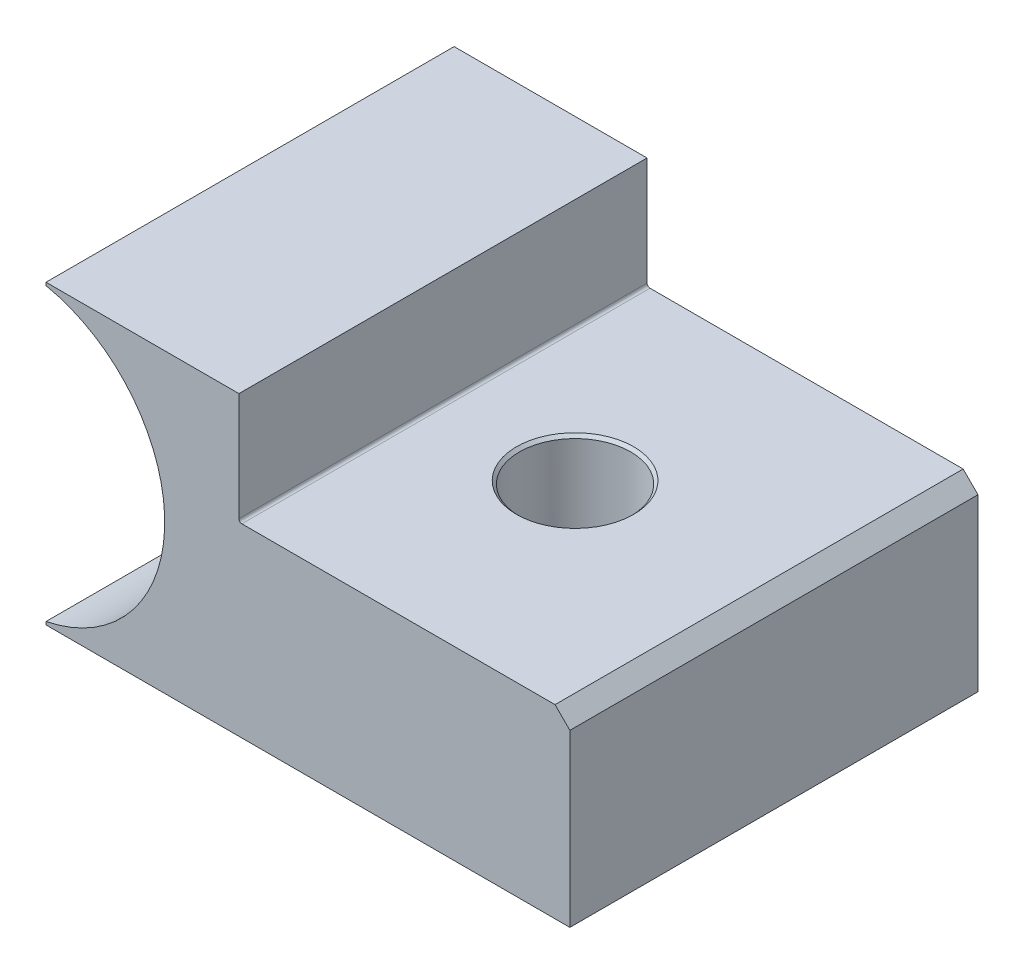
SolidWorks part; units mm, degrees
material "AISI Type A2 Tool Steel Custom"
ref_plane "Front Plane" through (0, 0, 0) normal (0, 0, 1) x (1, 0, 0)
ref_plane "Top Plane" through (0, 0, 0) normal (0, 1, 0) x (1, 0, 0)
ref_plane "Right Plane" through (0, 0, 0) normal (1, 0, 0) x (0, 0, -1)
sketch "Sketch1" plane through (0, 0, 0) normal (0, 0, 1) x (1, 0, 0)
  line L1 (2.54, 0) -> (47.371, 0)
  line L3 (2.54, 25.4) -> (19.05, 25.4)
  line L4 (47.371, 0) -> (47.371, 15.875)
  line L5 (2.54, 25.4) -> (2.54, 25.1434)
  line L6 (19.05, 25.4) -> (19.05, 15.875)
  line L7 (19.05, 15.875) -> (47.371, 15.875)
  line L8 (2.54, 0.2566) -> (2.54, 0)
  arc A1 (2.54, 0.2566) -> (2.54, 25.1434) centre (0, 12.7) ccw
  dimension "D2" = 25.4
  dimension "D1" = 16.51
  dimension "D3" = 9.525
  dimension "D4" = 2.54
  dimension "D5" = 28.321
  dimension "D6" = 15.875
  dimension "D7" = 0.2566
extrude "Boss-Extrude1" add sketch "Sketch1" along normal blind 34.925
sketch "Sketch2" plane through (0, 15.875, 0) normal (0, 1, 0) x (1, 0, 0)
  line L0 (0, -34.925) -> (0, 0) construction
  line L1 (2.54, -34.925) -> (2.54, 0) construction
  point P0 (30.353, -17.4625)
  point P5 (0, -17.4625)
  point P8 (2.54, -17.4625)
  dimension "D1" = 30.353
hole_wizard "3/8 (0.375) Diameter Hole1" positions "Sketch2" profile "Sketch4" hole size "3/8" standard "ANSI Inch" end condition through all
sketch "Sketch4" plane through (30.353, 15.875, 17.4625) normal (1, 0, 0) x (0, 0, 1)
  line L0 (0, 0) -> (0, 15.875)
  line L1 (0, 15.875) -> (4.7625, 15.875)
  line L2 (4.7625, 15.875) -> (4.7625, 0)
  line L5 (4.7625, 0) -> (0, 0)
  line L11 (0, -6.35) -> (0, 107.95) construction
  dimension "Thru Hole Dia." = 9.525
  dimension "Thru Hole Depth" = 15.875
chamfer "Chamfer1" distance 1.27 angle 45 1 edges at (47.371, 15.875, 17.4625)
chamfer "Chamfer2" distance 0.254 angle 45 1 edges at (30.353, 15.875, 22.225)
fillet "Fillet1" radius 0.254 1 edges at (19.05, 15.875, 17.4625)
